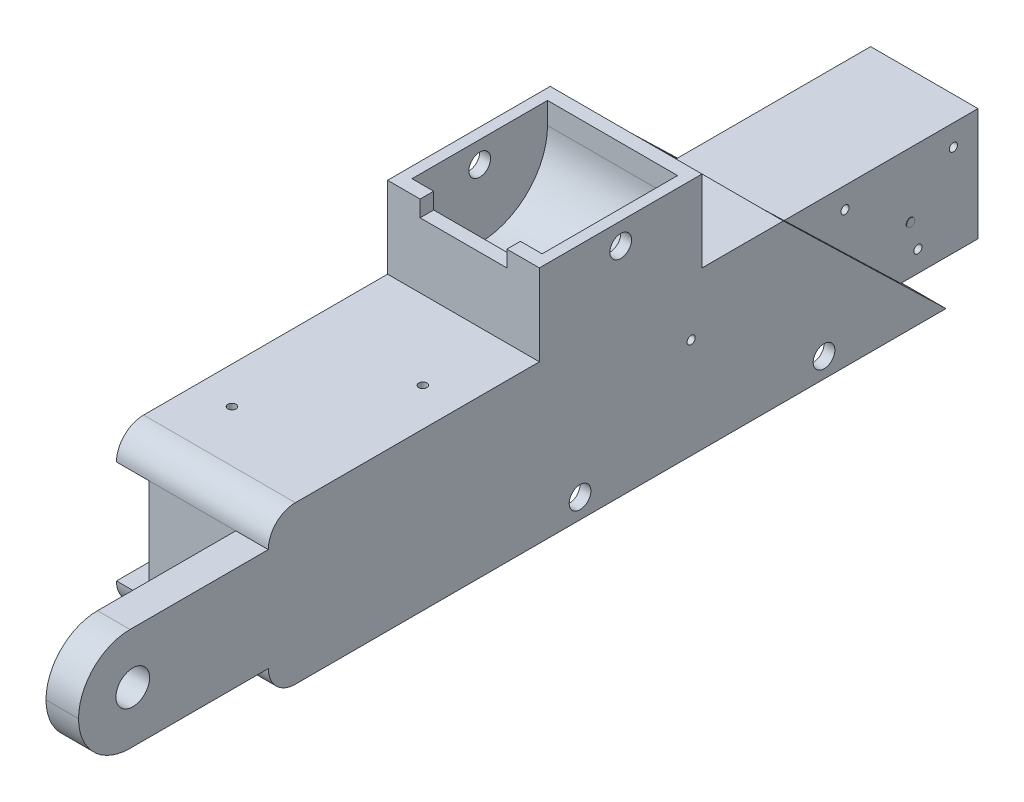
SolidWorks part; units mm, degrees
ref_plane "前视基准面" through (0, 0, 0) normal (0, 0, 1) x (1, 0, 0)
ref_plane "上视基准面" through (0, 0, 0) normal (0, 1, 0) x (1, 0, 0)
ref_plane "右视基准面" through (0, 0, 0) normal (1, 0, 0) x (0, 0, -1)
other "Configuration Table"
sketch "草图1" plane through (0, 0, 0) normal (1, 0, 0) x (0, 0, -1)
  line L0 (-150, 0) -> (150, 0) construction
  line L1 (-125, 14.5) -> (125, 14.5)
  line L2 (-125, 14.5) -> (-125, -14.5)
  line L3 (-125, -14.5) -> (125, -14.5)
  line L4 (125, 14.5) -> (125, -14.5)
  line L5 (-72.5, 29.5) -> (-72.5, 25.5)
  line L6 (-75, 14.5) -> (-45, 14.5)
  line L7 (-75, 14.5) -> (-75, 29.5)
  line L8 (-120, 10.8586) -> (120, 10.8586)
  line L9 (-120, 10.8586) -> (-120, -10.8586)
  line L10 (-120, -10.8586) -> (120, -10.8586)
  line L11 (120, 10.8586) -> (120, -10.8586)
  line L12 (-120, 10.8586) -> (120, -10.8586) construction
  line L13 (-120, -10.8586) -> (120, 10.8586) construction
  line L14 (-75, 29.5) -> (-45, 29.5)
  line L15 (-45, 14.5) -> (-45, 29.5)
  line L16 (-15, 14.5) -> (15, 14.5)
  line L17 (-15, 14.5) -> (-15, 29.5)
  line L18 (-15, 29.5) -> (15, 29.5)
  line L19 (15, 14.5) -> (15, 29.5)
  line L20 (45, 14.5) -> (75, 14.5)
  line L21 (45, 14.5) -> (45, 29.5)
  line L22 (45, 29.5) -> (75, 29.5)
  line L23 (75, 14.5) -> (75, 29.5)
  line L24 (-47.5, 29.5) -> (-47.5, 25.5)
  line L25 (-12.5, 29.5) -> (-12.5, 25.5)
  line L26 (12.5, 29.5) -> (12.5, 25.5)
  line L27 (47.5, 29.5) -> (47.5, 25.5)
  line L29 (72.5, 25.5) -> (72.5, 29.5)
  circle A2 centre (-67.5, -10.8586) radius 2
  circle A3 centre (-22.5, -10.8586) radius 2
  circle A4 centre (22.5, -10.8586) radius 2
  circle A5 centre (-60, 25.5) radius 2
  circle A6 centre (67.5, -10.8586) radius 2
  circle A7 centre (0, 25.5) radius 2
  circle A8 centre (60, 25.5) radius 2
  circle A9 centre (-60, 25.5) radius 12.5
  circle A10 centre (0, 25.5) radius 12.5
  circle A11 centre (60, 25.5) radius 12.5
  circle A12 centre (-67.5, -10.8586) radius 12.5
  circle A13 centre (-22.5, -10.8586) radius 12.5
  circle A14 centre (22.5, -10.8586) radius 12.5
  circle A15 centre (67.5, -10.8586) radius 12.5
  circle A16 centre (150, 0) radius 2
  circle A17 centre (-150, 0) radius 2
  circle A18 centre (-150, 0) radius 3.1
  point P10 (0, 0)
  point P12 (-125, 0)
  point P56 (-60, 29.5)
  point P62 (0, 29.5)
  point P64 (60, 29.5)
  dimension "D2" = 5
  dimension "D4" = 25
  dimension "D8" = 4
  dimension "D18" = 4
  dimension "D22" = 6.2
  dimension "D1" = 300
  dimension "D3" = 5
  dimension "D5" = 14.5
  dimension "D6" = 120
  dimension "D7" = 10.8586
  dimension "D9" = 52.5
  dimension "D10" = 45
  dimension "D11" = 45
  dimension "D12" = 45
  dimension "D13" = 60
  dimension "D14" = 60
  dimension "D15" = 60
  dimension "D16" = 60
  dimension "D17" = 52.5
  dimension "D19" = 30
  dimension "D20" = 4
  dimension "D21" = 15
extrude "凸台-拉伸1" add sketch "草图1" along normal blind 28 contours L1 L4 L3 L2 | L14 L15 L6 L7 | L18 L19 L16 L17 | L22 L23 L20 L21
extrude "切除-拉伸1" cut sketch "草图1<3>" along normal through all contours A2 | A3 | A4 | A6 | A8 | A7 | A5
sketch "草图1<3>" plane through (0, 0, 0) normal (1, 0, 0) x (0, 0, -1) same geometry as "草图1"
extrude "切除-拉伸2" cut sketch "草图1<5>" along normal offset from surface (24 mm away) 2 from offset 2 contours A9 L14 L5 | A9 L24 L14 | A10 L18 L25 | A10 L26 L18 | A11 L22 L27 | A11 L29 L22 | A12 | A9 | A13 | A10 | A14 | A11 | A15 region at (0, 28.5053, 72.3037) region at (0, 28.5053, 47.6963) region at (0, 28.5053, 12.3037) region at (0, 28.5053, -12.3037) region at (0, 28.5053, -47.6963) region at (0, 28.5053, -72.3037) up to face at (28, -10.8586, 65.5)
sketch "草图1<5>" plane through (0, 0, 0) normal (1, 0, 0) x (0, 0, -1) same geometry as "草图1"
sketch "草图3" plane through (0, 0, 125) normal (0, 0, 1) x (1, 0, 0)
  line L0 (28, 14.5) -> (28, -14.5) construction
  line L1 (28, 9.5) -> (22, 9.5)
  line L2 (28, 9.5) -> (28, -9.5)
  line L3 (28, -9.5) -> (22, -9.5)
  line L4 (22, 9.5) -> (22, -9.5)
  line L5 (28, 14.5) -> (0, 14.5) construction
  line L6 (28, -14.5) -> (0, -14.5) construction
  line L7 (0, 14.5) -> (0, -14.5) construction
  line L8 (0, 9.5) -> (6, 9.5)
  line L9 (0, 9.5) -> (0, -9.5)
  line L10 (0, -9.5) -> (6, -9.5)
  line L11 (6, 9.5) -> (6, -9.5)
  dimension "D1" = 6
  dimension "D2" = 5
  dimension "D3" = 5
extrude "凸台-拉伸2" add sketch "草图3" along normal blind 35 contours L1 L4 L3 L2
extrude "凸台-拉伸3" add sketch "草图3<3>" along normal blind 35 contours L2 L3 L4 L1 | L9 L10 L11 L8
sketch "草图3<3>" plane through (0, 0, 125) normal (0, 0, 1) x (1, 0, 0) same geometry as "草图3"
extrude "切除-拉伸3" cut sketch "草图1<6>" along normal through all contours A17
sketch "草图1<6>" plane through (0, 0, 0) normal (1, 0, 0) x (0, 0, -1) same geometry as "草图1"
extrude "切除-拉伸7" cut sketch "草图1<8>" along normal up to next contours A18
sketch "草图1<8>" plane through (0, 0, 0) normal (1, 0, 0) x (0, 0, -1) same geometry as "草图1"
fillet "圆角1" radius 9.5 4 edges at (25, 9.5, 160) (25, -9.5, 160) (3, -9.5, 160) (3, 9.5, 160)
fillet "圆角2" radius 5 2 edges at (14, -14.5, 125) (14, 14.5, 125)
sketch "草图4" plane through (0, 0, -125) normal (0, 0, -1) x (-1, 0, 0)
  line L1 (-28, 14.5) -> (0, 14.5) construction
  circle A0 centre (-14, 0) radius 5.1
  point P7 (-14, 14.5)
  dimension "D1" = 10.2
extrude "切除-拉伸4" cut sketch "草图4" against normal blind 31.5
extrude "切除-拉伸5" cut sketch "草图4<2>" against normal offset from surface (21.5 mm away) 10 flip side to cut up to face at (8.9, 0, -93.5)
sketch "草图4<2>" plane through (0, 0, -125) normal (0, 0, -1) x (-1, 0, 0) same geometry as "草图4"
sketch "草图5" plane through (0, 0, -103.5) normal (0, 0, -1) x (-1, 0, 0)
  line L0 (-28, 14.5) -> (0, 14.5) construction
  line L1 (-25.9, -12.4) -> (-2.1, -12.4)
  line L2 (-25.9, -12.4) -> (-25.9, 12.4)
  line L3 (-25.9, 12.4) -> (-2.1, 12.4)
  line L4 (-2.1, -12.4) -> (-2.1, 12.4)
  line L5 (-25.9, -12.4) -> (-2.1, 12.4) construction
  line L6 (-25.9, 12.4) -> (-2.1, -12.4) construction
  line L7 (0, -14.5) -> (0, 14.5) construction
  circle A0 centre (-14, 0) radius 5.1 construction
  point P0 (-14, 0)
  dimension "D1" = 2.1
  dimension "D2" = 2.1
extrude "切除-拉伸6" cut sketch "草图5" against normal blind 18 flip side to cut contours L3 L4 L1 L2
sketch "草图6" plane through (0, 14.5, 0) normal (0, 1, 0) x (1, 0, 0)
  circle A0 centre (7, 23.5) radius 0.75
  circle A1 centre (21, 35.5) radius 0.75
  circle A2 centre (7, -23.5) radius 0.75
  circle A3 centre (21, -35.5) radius 0.75
  dimension "D1" = 1.5
extrude "切除-拉伸8" cut sketch "草图6" against normal blind 4 contours A2 | A3 | A0 | A1
sketch "草图7" plane through (0, 14.5, 0) normal (0, 1, 0) x (1, 0, 0)
  circle A0 centre (7, -89.5) radius 0.75
  circle A1 centre (21.2, -110.5) radius 0.75
  dimension "D1" = 1.5
extrude "切除-拉伸9" cut sketch "草图7" against normal blind 4 contours A0 | A1
sketch "草图8" plane through (0, 0, 0) normal (-1, 0, 0) x (0, 0, 1)
  circle A0 centre (47, 4) radius 0.75
  circle A1 centre (2.499, -1.5) radius 0.75
  dimension "D1" = 1.5
extrude "切除-拉伸10" cut sketch "草图8" against normal blind 4
sketch "草图9" plane through (28, 0, 0) normal (1, 0, 0) x (0, 0, -1)
  circle A0 centre (-107.5, -0.5) radius 0.75
  circle A1 centre (-92.5, -0.5) radius 0.75
  dimension "D1" = 1.5
extrude "切除-拉伸11" cut sketch "草图9" against normal blind 4 contours A0 | A1
sketch "草图10" plane through (0, 0, 0) normal (-1, 0, 0) x (0, 0, 1)
  line L0 (30, 14.5) -> (0, -14.5)
  line L1 (45, 14.5) -> (15, 14.5) construction
  line L2 (120, -14.5) -> (-85.5, -14.5) construction
  line L3 (30, 14.5) -> (30, 45.5421)
  line L4 (30, 45.5421) -> (207.4503, 45.5421)
  line L5 (207.4503, 45.5421) -> (207.4503, -65.6361)
  line L6 (207.4503, -65.6361) -> (0, -65.6361)
  line L7 (0, -65.6361) -> (0, -14.5)
  line L8 (30, 45.5421) -> (-140.4585, 45.5421)
  line L9 (30, 14.5) -> (-10, 14.5)
  line L10 (30, 14.5) -> (30, -14.5)
  line L11 (30, -14.5) -> (-10, -14.5)
  line L12 (-10, 14.5) -> (-10, -14.5)
  line L13 (-140.4585, 45.5421) -> (-140.4585, -65.6361)
  line L14 (-140.4585, -65.6361) -> (-10, -65.6361)
  line L15 (-10, -65.6361) -> (-10, -14.5)
  circle M8 centre (2.499, -1.5) radius 0.75
  circle M12 centre (0, 25.5) radius 2
  circle M13 centre (-60, 25.5) radius 2
  circle M14 centre (-67.5, -10.8586) radius 2
  circle M15 centre (-22.5, -10.8586) radius 2
  line M17 (-85.5, 14.5) -> (-85.5, -14.5)
  line M18 (-85.5, -14.5) -> (120, -14.5)
  line M29 (45, 14.5) -> (15, 14.5)
  line M30 (15, 14.5) -> (15, 29.5)
  line M31 (15, 29.5) -> (-15, 29.5)
  line M32 (-15, 29.5) -> (-15, 14.5)
  line M33 (-15, 14.5) -> (-45, 14.5)
  line M34 (-45, 14.5) -> (-45, 29.5)
  line M35 (-45, 29.5) -> (-75, 29.5)
  line M36 (-75, 29.5) -> (-75, 14.5)
  line M37 (-75, 14.5) -> (-85.5, 14.5)
  dimension "D1" = 40
sketch "草图11" plane through (0, 0, 0) normal (1, 0, 0) x (0, 0, -1)
  line L0 (-30, 14.5) -> (0, -14.5) construction
  line L1 (-45, 14.5) -> (-15, 14.5) construction
  line L2 (-120, -14.5) -> (85.5, -14.5) construction
  circle A0 centre (-14.5301, 6.5) radius 0.75
  circle A1 centre (-1.0818, -6.5) radius 0.75
  circle A2 centre (-14.5301, 6.5) radius 2.5
  circle A3 centre (-1.0818, -6.5) radius 2.5
  circle A4 centre (-14.5301, 6.5) radius 1.8
  circle A5 centre (-1.0818, -6.5) radius 1.8
  circle A6 centre (5.4699, 6.5) radius 0.75
  circle A7 centre (5.4699, 6.5) radius 2.5
  circle A8 centre (5.4699, 6.5) radius 1.8
  dimension "D3" = 1.5
  dimension "D4" = 3.6
  dimension "D5" = 5
  dimension "D1" = 5
  dimension "D2" = 5
  dimension "D6" = 8
  dimension "D7" = 8
  dimension "D8" = 20
extrude "切除-拉伸12" cut sketch "草图11" along normal through all contours A1 | A0 | A6
extrude "切除-拉伸14" cut sketch "草图10" against normal through all contours L14 L15 L3 L8 L13 M18 M17 M37 M36 M35 M34 M33 M32 M31 M30 M29 | L12 L9 M30 M31 M32 M33 M34 M35 M36 M37 M17 M18 M12 M14 M15 M13 region at (0, 16.5351, 22.5) region at (0, 6.3937, -42.6633)
extrude "切除-拉伸15" cut sketch "草图10<5>" against normal blind 4.1 contours L9 L12 L0 M18 M29 M8 region at (0, 2.9108, 4.0037)
sketch "草图10<5>" plane through (0, 0, 0) normal (-1, 0, 0) x (0, 0, 1) same geometry as "草图10"
extrude "切除-拉伸16" cut sketch "草图10<6>" along normal blind 4.1 from surface contours L9 L12 L0 M18 M29 M8 | M8 region at (0, 2.9108, 4.0037) region at (0, -1.5, 2.499) starting at face at (28, 6.7692, 90.5389)
sketch "草图10<6>" plane through (0, 0, 0) normal (-1, 0, 0) x (0, 0, 1) same geometry as "草图10"
sketch "草图13" plane through (0, 14.5, 0) normal (0, 1, 0) x (1, 0, 0)
  line L0 (4.1, -30) -> (0, -30) construction
  line L1 (4.1, -30) -> (23.9, -30)
  line L2 (4.1, -30) -> (4.1, 10)
  line L3 (4.1, 10) -> (23.9, 10)
  line L4 (23.9, -30) -> (23.9, 10)
  line L5 (4.1, -30) -> (4.1, -5.9372) construction
extrude "切除-拉伸17" cut sketch "草图13" against normal blind 4.1
sketch "草图14" plane through (0, -14.5, 0) normal (0, -1, 0) x (1, 0, 0)
  line L0 (4.1, 0) -> (0, 0) construction
  line L1 (4.1, 0) -> (23.9, 0)
  line L2 (4.1, 0) -> (4.1, -10)
  line L3 (4.1, -10) -> (23.9, -10)
  line L4 (23.9, 0) -> (23.9, -10)
  line L5 (4.1, -10) -> (4.1, 0) construction
extrude "切除-拉伸18" cut sketch "草图14" against normal blind 4.1
sketch "草图15" plane through (0, 0, 0) normal (-1, 0, 0) x (0, 0, 1)
  line L0 (0, -10.4) -> (0, -14.5)
  line L1 (0, -14.5) -> (4.2414, -10.4)
  line L2 (30, 14.5) -> (0, -14.5) construction
  line L4 (4.2414, -10.4) -> (0, -10.4)
  line L5 (0, -10.4) -> (-10, -10.4) construction
extrude "切除-拉伸19" cut sketch "草图15" against normal through all
sketch "草图16" plane through (0, 29.5, 0) normal (0, 1, 0) x (1, 0, 0)
  line L0 (28, -75) -> (0, -75) construction
  line L1 (6, -77.5) -> (22, -77.5)
  line L2 (6, -77.5) -> (6, -72.5)
  line L3 (6, -72.5) -> (22, -72.5)
  line L4 (22, -77.5) -> (22, -72.5)
  line L5 (6, -77.5) -> (22, -72.5) construction
  line L6 (6, -72.5) -> (22, -77.5) construction
  line L7 (26, -72.5) -> (2, -72.5) construction
  line L8 (26, -47.5) -> (26, -72.5) construction
  line L9 (6, -72.5) -> (22, -72.5)
  line L10 (6, -72.5) -> (6, -60)
  line L11 (6, -60) -> (22, -60)
  line L12 (22, -72.5) -> (22, -60)
  point P0 (14, -75)
  point P7 (14, -75)
  point P14 (26, -60)
  line M10 (0, -75) -> (28, -75)
  line M13 (26, -72.5) -> (2, -72.5)
  dimension "D1" = 16
extrude "切除-拉伸20" cut sketch "草图16" against normal blind 3 contours L1 L4 L2 M10 | L4 L2 M10 M13 | L12 L11 L10 M13 region at (14, 29.5, 76.25) region at (14, 29.5, 73.75) region at (14, 29.5, 66.25)
sketch "草图18" plane through (28, 0, 0) normal (1, 0, 0) x (0, 0, -1)
  line L0 (-150.5, 9.5) -> (-125, 9.5) construction
  line L1 (-160, 9.5) -> (-112.5, 9.5)
  line L2 (-160, 9.5) -> (-160, -9.5)
  line L3 (-160, -9.5) -> (-112.5, -9.5)
  line L4 (-112.5, 9.5) -> (-112.5, -9.5)
  line L5 (-150.5, -9.5) -> (-125, -9.5) construction
  arc A0 (-150.5, 9.5) -> (-160, 0) centre (-150.5, 0) ccw construction
  circle A1 centre (-107.5, -0.5) radius 0.75 construction
  circle A2 centre (-119.5, 4.5) radius 1.5
  circle A3 centre (-119.5, 4.5) radius 0.75
  circle A4 centre (-119.5, 4.5) radius 2.25
  circle A5 centre (-119.5, -4.5) radius 0.75
  circle A6 centre (-119.5, -4.5) radius 1.5
  circle A7 centre (-119.5, -4.5) radius 2.25
  dimension "D1" = 5
  dimension "D2" = 4.5
  dimension "D3" = 3
  dimension "D4" = 1.5
  dimension "D5" = 7
  dimension "D6" = 5
  dimension "D7" = 5
extrude "切除-拉伸21" cut sketch "草图18" against normal up to surface (6 mm away) contours L1 L4 L3 L2 up to face at (22, 2, 150)
extrude "切除-拉伸22" cut sketch "草图18<3>" against normal blind 4 from surface contours A3 | A5 starting at face at (22, 0, 118.75)
sketch "草图18<3>" plane through (28, 0, 0) normal (1, 0, 0) x (0, 0, -1) same geometry as "草图18"
ref_plane "基准面1" through (-10, 0, 0) normal (1, 0, 0) x (0, 0, -1)
sketch "草图17" plane through (-10, 0, 0) normal (1, 0, 0) x (0, 0, -1)
  line L1 (-200, -100) -> (200, -100)
  line L2 (-200, -100) -> (-200, 100)
  line L3 (-200, 100) -> (200, 100)
  line L4 (200, -100) -> (200, 100)
  line L5 (-200, -100) -> (200, 100) construction
  line L6 (-200, 100) -> (200, -100) construction
  point P0 (0, 0)
  dimension "D1" = 400
  dimension "D2" = 200
mirror "镜向1" about plane through (-10, 0, 0) normal (1, 0, 0) of bodies 158
extrude "切除-拉伸23" cut sketch "草图17" along normal through all
